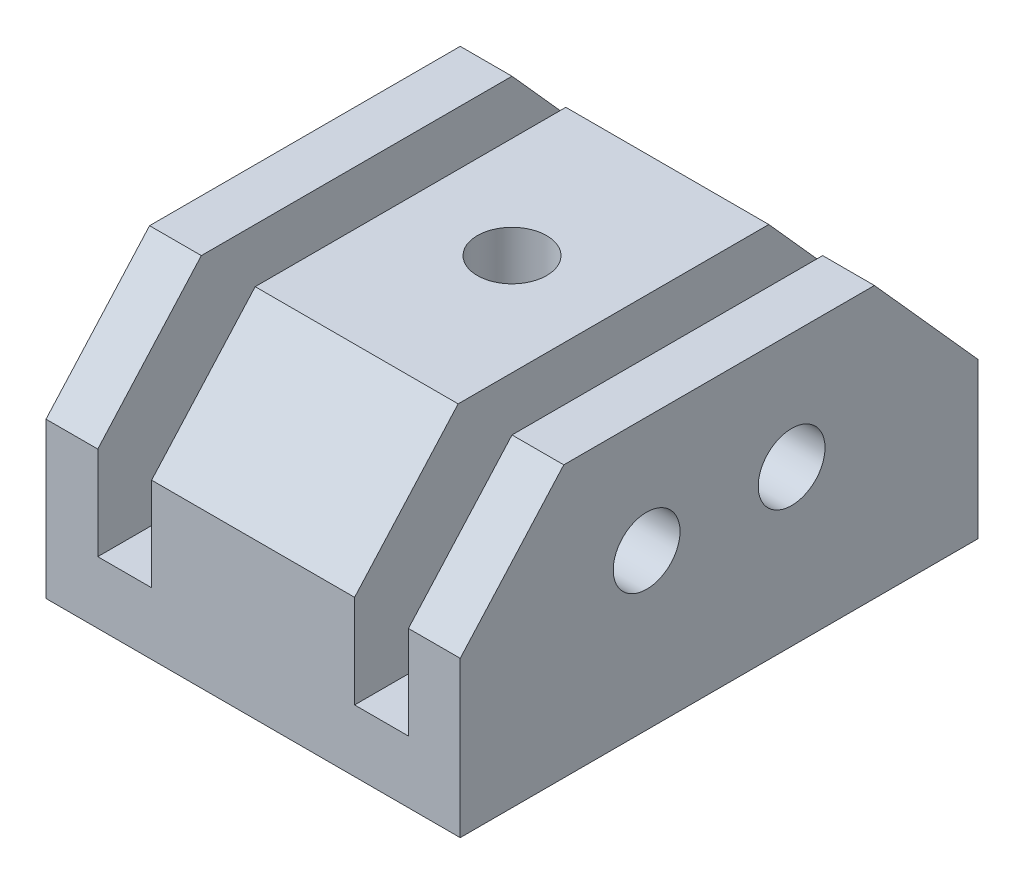
SolidWorks part; units mm, degrees
ref_plane "Front Plane" through (0, 0, 0) normal (0, 0, 1) x (1, 0, 0)
ref_plane "Top Plane" through (0, 0, 0) normal (0, 1, 0) x (1, 0, 0)
ref_plane "Right Plane" through (0, 0, 0) normal (1, 0, 0) x (0, 0, -1)
sketch "Sketch1" plane through (0, 0, 0) normal (1, 0, 0) x (0, 0, -1)
  line L1 (0, 0) -> (63.5, 0)
  line L2 (0, 0) -> (0, 6.35)
  line L3 (0, 6.35) -> (63.5, 6.35)
  line L4 (63.5, 0) -> (63.5, 6.35)
  dimension "D1" = 6.35
  dimension "D2" = 63.5
extrude "Boss-Extrude1" add sketch "Sketch1" against normal blind 50.8
sketch "Sketch2" plane through (0, 0, 0) normal (1, 0, 0) x (0, 0, -1)
  line L0 (0, 6.35) -> (0, 19.05)
  line L1 (0, 19.05) -> (12.7, 33.249)
  line L2 (12.7, 33.249) -> (50.8, 33.249)
  line L3 (50.8, 33.249) -> (63.5, 19.05)
  line L4 (63.5, 19.05) -> (63.5, 6.35)
  line L5 (63.5, 6.35) -> (0, 6.35)
  point P7 (31.75, 33.249)
  point P10 (31.75, 6.35)
  dimension "D1" = 38.1
  dimension "D2" = 12.7
  dimension "D3" = 12.7
  dimension "D4" = 19.05
  dimension "D5" = 19.05
extrude "Boss-Extrude2" add sketch "Sketch2" against normal blind 50.8
sketch "Sketch10" plane through (0, 0, -63.5) normal (0, 0, -1) x (-1, 0, 0)
  line L1 (50.8, 33.249) -> (0, 33.249) construction
  line L3 (6.35, 7.62) -> (6.35, 33.249)
  line L4 (6.35, 33.249) -> (12.954, 33.249)
  line L5 (12.954, 7.62) -> (12.954, 33.249)
  line L6 (6.35, 7.62) -> (12.954, 7.62)
  line L8 (50.8, 0) -> (0, 0) construction
  point P11 (12.954, 7.62)
  dimension "D1" = 7.62
  dimension "D2" = 6.604
  dimension "D3" = 6.35
extrude "Cut-Extrude1" cut sketch "Sketch10" against normal through all
pattern_linear "LPattern3" count 2 spacing 31.496 along (-1, 0, 0) of "Cut-Extrude1"
sketch "Sketch11" plane through (0, 0, 0) normal (1, 0, 0) x (0, 0, -1)
  circle A0 centre (22.86, 19.05) radius 4.0957
  circle A1 centre (22.86, 19.05) radius 7.9375 construction
  circle A2 centre (40.64, 19.05) radius 4.0958
  circle A3 centre (40.64, 19.05) radius 7.9375 construction
  dimension "D1" = 8.1915
  dimension "D3" = 15.875
  dimension "D4" = 8.1915
  dimension "D6" = 15.875
  dimension "D2" = 10.16
  dimension "D5" = 10.16
extrude "Cut-Extrude2" cut sketch "Sketch11" against normal through all
sketch "Sketch14" plane through (0, 33.249, 0) normal (0, 1, 0) x (1, 0, 0)
  line L3 (-37.846, 12.7) -> (-37.846, 50.8) construction
  point P0 (-25.4, 31.75)
  point P4 (-37.846, 31.75)
  dimension "D1" = 12.446
sketch "Sketch17" plane through (0, 40.0201, -44.7438) normal (0, 0.6667, -0.7454) x (-1, 0, 0)
  line L0 (12.954, -28.1343) -> (12.954, -9.0843) construction
  line L1 (37.846, -9.0843) -> (12.954, -9.0843) construction
  point P0 (25.4, -18.6093)
  point P4 (12.954, -18.6093)
  point P7 (25.4, -9.0843)
sketch "Sketch18" plane through (0, 8.4667, 9.466) normal (0, 0.6667, 0.7454) x (1, 0, 0)
  line L0 (-12.954, 33.249) -> (-12.954, 14.199) construction
  line L1 (-37.846, 33.249) -> (-12.954, 33.249) construction
  point P0 (-25.4, 23.724)
  point P1 (-25.4, 23.724)
  point P4 (-12.954, 23.724)
  point P7 (-25.4, 33.249)
ref_plane "Plane2" through (0, 33.02, 0) normal (0, -1, 0) x (-1, 0, 0)
fillet "Fillet1" [suppressed] radius 2.54
sketch "Sketch19" plane through (0, 0, 0) normal (0, -1, 0) x (1, 0, 0)
  line L0 (-24.6552, -63.5) -> (-24.6552, 0) construction
  line L1 (-50.8, -63.5) -> (0, -63.5) construction
  line L2 (-50.8, 0) -> (0, 0) construction
  line L3 (0, -31.75) -> (-50.8, -31.75) construction
  line L4 (0, 0) -> (0, -63.5) construction
  line L5 (-50.8, 0) -> (-50.8, -63.5) construction
  line L7 (-3.4052, -53) -> (-45.9052, -53)
  line L8 (-3.4052, -53) -> (-3.4052, -10.5)
  line L9 (-3.4052, -10.5) -> (-45.9052, -10.5)
  line L10 (-45.9052, -53) -> (-45.9052, -10.5)
  line L11 (-3.4052, -53) -> (-45.9052, -10.5) construction
  line L12 (-3.4052, -10.5) -> (-45.9052, -53) construction
  point P12 (-24.6552, -31.75)
  dimension "D1" = 42.5
extrude "Cut-Extrude3" cut sketch "Sketch19" against normal blind 5.08
sketch "Sketch21" plane through (0, 0, 0) normal (0, -1, 0) x (1, 0, 0)
  line L0 (-25.4, -63.5) -> (-25.4, 0) construction
  line L1 (-50.8, -63.5) -> (0, -63.5) construction
  line L2 (-50.8, 0) -> (0, 0) construction
  line L3 (-50.8, -31.75) -> (0, -31.75) construction
  line L4 (-50.8, 0) -> (-50.8, -63.5) construction
  line L5 (0, 0) -> (0, -63.5) construction
  circle A0 centre (-40.9, -47.25) radius 1.7
  circle A1 centre (-40.9, -16.25) radius 1.7
  circle A2 centre (-9.9, -16.25) radius 1.7
  circle A3 centre (-9.9, -47.25) radius 1.7
  point P14 (-25.4, -31.75)
  point P24 (-25.4, -31.75)
  dimension "D1" = 3.4
  dimension "D3" = 15.5
  dimension "D2" = 15.5
  dimension "D4" = 4
extrude "Cut-Extrude4" cut sketch "Sketch21" against normal up to next
sketch "Sketch22" plane through (0, 0, 0) normal (0, -1, 0) x (1, 0, 0)
  line L1 (-25.4, -63.5) -> (-25.4, 0) construction
  line L2 (-50.8, -63.5) -> (0, -63.5) construction
  line L3 (-50.8, 0) -> (0, 0) construction
  line L4 (0, -31.75) -> (-50.8, -31.75) construction
  line L6 (0, 0) -> (0, -63.5) construction
  line L7 (-50.8, 0) -> (-50.8, -63.5) construction
  circle A1 centre (-25.4, -31.75) radius 11
  dimension "D1" = 22
extrude "Cut-Extrude5" cut sketch "Sketch22" against normal blind 3 from surface starting at face at (-9.9, 5.08, -48.95)
sketch "Sketch23" plane through (0, 0, 0) normal (0, -1, 0) x (1, 0, 0)
  circle A0 centre (-25.4, -31.75) radius 4.25
extrude "Cut-Extrude6" cut sketch "Sketch23" against normal through all
